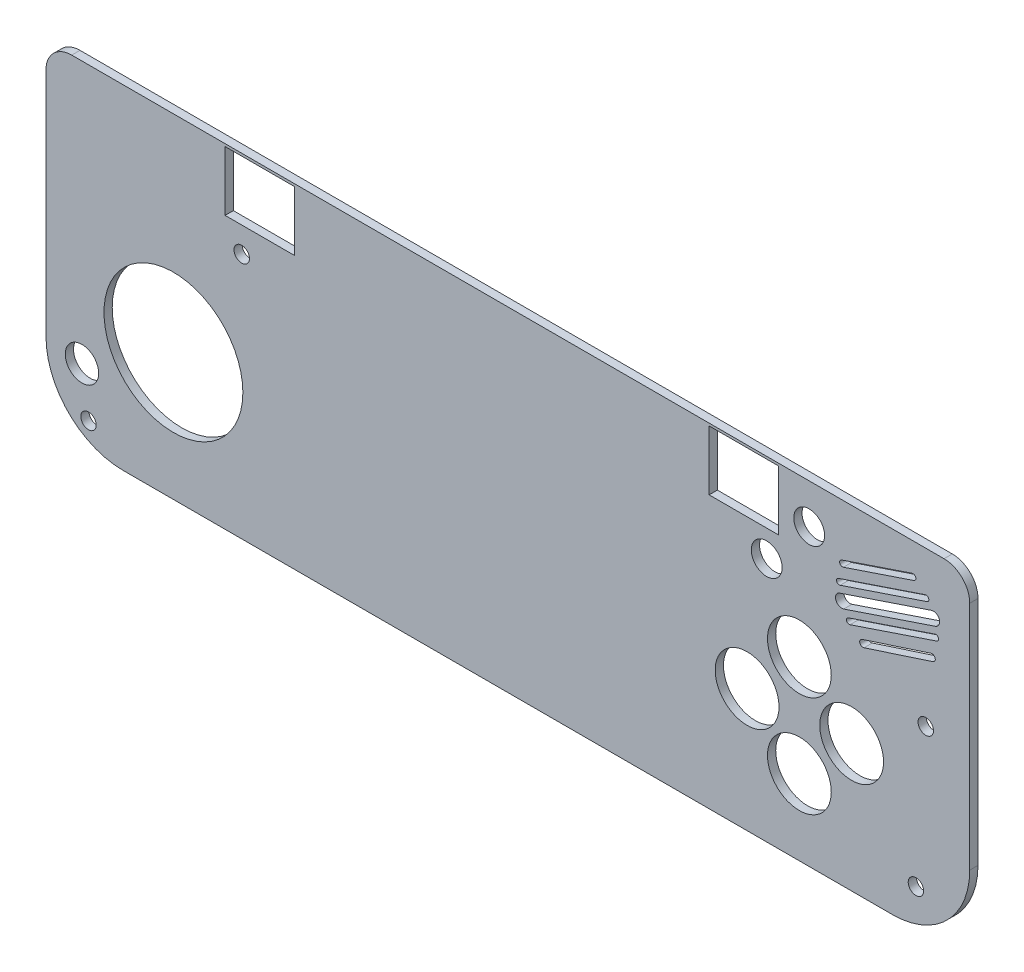
SolidWorks part; units mm, degrees
other "Caméra1"
ref_plane "Plan de face" through (0, 0, 0) normal (0, 0, 1) x (1, 0, 0)
ref_plane "Plan de dessus" through (0, 0, 0) normal (0, 1, 0) x (1, 0, 0)
ref_plane "Plan de droite" through (0, 0, 0) normal (1, 0, 0) x (0, 0, -1)
sketch "Esquisse20" plane through (0, 0, 0) normal (0, 0, 1) x (1, 0, 0)
  line L1 (15, -2.2) -> (164.57, -2.2)
  line L2 (0, 12.8) -> (0, 57.73)
  line L3 (5, 62.73) -> (174.57, 62.73)
  line L4 (179.57, 12.8) -> (179.57, 57.73)
  arc A0 (0, 57.73) -> (5, 62.73) centre (5, 57.73) cw
  arc A1 (174.57, 62.73) -> (179.57, 57.73) centre (174.57, 57.73) cw
  arc A2 (164.57, -2.2) -> (179.57, 12.8) centre (164.57, 12.8) ccw
  arc A3 (15, -2.2) -> (0, 12.8) centre (15, 12.8) cw
  point P0 (1.4645, 61.2655)
  point P7 (0, 62.73)
  point P10 (179.57, 62.73)
  point P14 (179.57, -2.2)
  point P17 (0, -2.2)
extrude "Boss.-Extru.1" add sketch "Esquisse20" along normal blind 1.6051
sketch "Esquisse22" plane through (0, 0, 1.6051) normal (0, 0, 1) x (1, 0, 0)
  line L0 (15, -2.2) -> (164.57, -2.2) construction
  line L1 (0, 57.73) -> (0, 12.8) construction
  circle A0 centre (24.77, 22.57) radius 13.5
  dimension "D1" = 24.77
  dimension "D2" = 24.77
extrude "Enlèv. mat.-Extru.1" cut sketch "Esquisse22" against normal blind 2.5
sketch "Esquisse23" plane through (0, 0, 1.6051) normal (0, 0, 1) x (1, 0, 0)
  line L0 (15, -2.2) -> (164.57, -2.2) construction
  line L1 (0, 57.73) -> (0, 12.8) construction
  circle A0 centre (6.99, 11.77) radius 3.25
  circle A1 centre (-24.9782, 23.5691) radius 3.25
  dimension "D1" = 13.97
  dimension "D2" = 6.99
extrude "Enlèv. mat.-Extru.2" cut sketch "Esquisse23" against normal blind 2.5
sketch "Esquisse24" plane through (0, 0, 1.6051) normal (0, 0, 1) x (1, 0, 0)
  line L0 (34.82, 59.37) -> (48.32, 50.65)
  line L1 (34.82, 59.37) -> (48.32, 59.37)
  line L2 (34.82, 59.37) -> (34.82, 50.65)
  line L3 (34.82, 50.65) -> (48.32, 50.65)
  line L4 (48.32, 59.37) -> (48.32, 50.65)
  line L5 (179.57, 12.8) -> (179.57, 57.73) construction
  line L7 (174.57, 62.73) -> (5, 62.73) construction
  point P4 (41.57, 55.01)
  dimension "D1" = 13.5
  dimension "D2" = 8.72
  dimension "D3" = 138
  dimension "D4" = 7.72
extrude "Enlèv. mat.-Extru.3" cut sketch "Esquisse24" against normal blind 2.5 contours L2 L3 L0 | L4 L1 L0 region at (43.82, 56.4633, 1.6051) region at (39.32, 53.5567, 1.6051)
sketch "Esquisse25" plane through (0, 0, 1.6051) normal (0, 0, 1) x (1, 0, 0)
  line L0 (48.32, 59.37) -> (34.82, 59.37)
  line L1 (48.32, 59.37) -> (48.32, 62.2418)
  line L2 (34.82, 59.37) -> (34.82, 62.2418)
  line L3 (48.32, 62.2418) -> (34.82, 62.2418)
extrude "Enlèv. mat.-Extru.4" cut sketch "Esquisse25" against normal blind 2.5
fillet "Congé1" radius 2 rebuild error yes
sketch "Esquisse26" plane through (0, 0, 1.6051) normal (0, 0, 1) x (1, 0, 0)
  line L0 (179.57, 12.8) -> (179.57, 57.73) construction
  line L1 (174.57, 62.73) -> (5, 62.73) construction
  circle A1 centre (156.61, 22.63) radius 6.2
  dimension "D2" = 22.96
  dimension "D3" = 40.1
sketch "Esquisse27" plane through (0, 0, 1.6051) normal (0, 0, 1) x (1, 0, 0)
  line L0 (179.57, 12.8) -> (179.57, 57.73) construction
  line L1 (174.57, 62.73) -> (5, 62.73) construction
  circle A0 centre (146.45, 12.47) radius 6.2
  circle A1 centre (136.29, 21.73) radius 6.2
  circle A2 centre (146.45, 32.15) radius 6.2
  dimension "D1" = 33.12
  dimension "D2" = 43.28
  dimension "D3" = 33.12
  dimension "D4" = 30.58
  dimension "D5" = 41
  dimension "D6" = 50.26
extrude "Enlèv. mat.-Extru.5" cut sketch "Esquisse26" against normal blind 2.5
extrude "Enlèv. mat.-Extru.6" cut sketch "Esquisse27" against normal blind 2.5
sketch "Esquisse30" plane through (0, 0, 1.6051) normal (0, 0, 1) x (1, 0, 0)
  line L0 (128.91, 59.37) -> (142.41, 50.65)
  line L1 (128.91, 59.37) -> (142.41, 59.37)
  line L2 (128.91, 59.37) -> (128.91, 50.65)
  line L3 (128.91, 50.65) -> (142.41, 50.65)
  line L4 (142.41, 59.37) -> (142.41, 50.65)
  line L5 (142.41, 59.37) -> (128.91, 50.65)
  line L6 (174.57, 62.73) -> (5, 62.73) construction
  line L7 (179.57, 12.8) -> (179.57, 57.73) construction
  line L8 (142.41, 59.37) -> (128.91, 59.37)
  line L9 (142.41, 59.37) -> (142.41, 62.2543)
  line L10 (128.91, 59.37) -> (128.91, 62.2543)
  line L11 (142.41, 62.2543) -> (128.91, 62.2543)
  point P4 (135.66, 55.01)
  line M7 (174.57, 62.73) -> (5, 62.73)
  dimension "D1" = 13.5
  dimension "D2" = 8.72
  dimension "D3" = 7.72
  dimension "D4" = 43.91
extrude "Enlèv. mat.-Extru.7" cut sketch "Esquisse30" against normal blind 2.5 contours L10 L1 L9 M7 | L5 L1 L0 | L5 L0 L2 | L0 L5 L3 | L4 L5 L0 region at (135.66, 57.9167, 1.6051) region at (135.66, 60.8122, 1.6051) region at (131.16, 55.01, 1.6051) region at (140.16, 55.01, 1.6051) region at (135.66, 52.1033, 1.6051)
fillet "Congé2" radius 2 rebuild error yes
sketch "Esquisse31" plane through (0, 0, 1.6051) normal (0, 0, 1) x (1, 0, 0)
  line L0 (174.57, 62.73) -> (5, 62.73) construction
  line L1 (179.57, 12.8) -> (179.57, 57.73) construction
  circle A0 centre (148.36, 55.01) radius 3
  circle A1 centre (140.1, 45.49) radius 3
  dimension "D1" = 7.72
  dimension "D3" = 17.24
  dimension "D2" = 31.21
  dimension "D4" = 39.47
extrude "Enlèv. mat.-Extru.8" cut sketch "Esquisse31" against normal blind 2.5
sketch "Esquisse32" plane through (0, 0, 1.6051) normal (0, 0, 1) x (1, 0, 0)
  line L0 (179.57, 12.8) -> (179.57, 57.73) construction
  line L1 (174.57, 62.73) -> (5, 62.73) construction
  line L2 (172.5084, 51.66) -> (154.6916, 45.66) construction
  line L3 (172.8949, 50.5123) -> (155.0781, 44.5123)
  line L4 (172.1219, 52.8077) -> (154.3051, 46.8077)
  line L5 (154.2, 48.66) -> (171.0851, 54.3462) construction
  line L6 (154.0321, 49.1585) -> (170.9172, 54.8448)
  line L7 (154.3679, 48.1615) -> (171.253, 53.8477)
  line L8 (154.8275, 52.0369) -> (168.5427, 56.6556) construction
  line L9 (154.6512, 52.5603) -> (168.3664, 57.1791)
  line L10 (155.0038, 51.5134) -> (168.719, 56.1321)
  line L11 (156.1149, 42.9738) -> (173, 48.66) construction
  line L12 (155.9468, 43.4729) -> (172.8319, 49.1592)
  line L13 (156.283, 42.4746) -> (173.1681, 48.1608)
  line L14 (158.8161, 40.5684) -> (172.2294, 44.9325) construction
  line L17 (158.6179, 41.1774) -> (172.0312, 45.5415)
  line L18 (159.0142, 39.9594) -> (172.4275, 44.3235)
  circle A0 centre (163.6, 48.66) radius 10
  circle A1 centre (163.6, 48.66) radius 9.4
  arc A2 (172.8949, 50.5123) -> (172.1219, 52.8077) centre (172.5084, 51.66) ccw
  arc A3 (154.3051, 46.8077) -> (155.0781, 44.5123) centre (154.6916, 45.66) ccw
  arc A4 (154.0321, 49.1585) -> (154.3679, 48.1615) centre (154.2, 48.66) ccw
  arc A5 (171.253, 53.8477) -> (170.9172, 54.8448) centre (171.0851, 54.3462) ccw
  arc A6 (154.6512, 52.5603) -> (155.0038, 51.5134) centre (154.8275, 52.0369) ccw
  arc A7 (168.719, 56.1321) -> (168.3664, 57.1791) centre (168.5427, 56.6556) ccw
  arc A8 (155.9468, 43.4729) -> (156.283, 42.4746) centre (156.1149, 42.9738) ccw
  arc A9 (173.1681, 48.1608) -> (172.8319, 49.1592) centre (173, 48.66) ccw
  arc A12 (158.6179, 41.1774) -> (159.0142, 39.9594) centre (158.8161, 40.5684) ccw
  arc A13 (172.4275, 44.3235) -> (172.0312, 45.5415) centre (172.2294, 44.9325) ccw
  point P9 (163.6, 48.66)
  point P16 (162.6426, 51.5031)
  point P23 (161.6851, 54.3462)
  point P30 (164.5574, 45.8169)
  point P37 (165.5227, 42.7505)
  dimension "D1" = 15.97
  dimension "D3" = 0.589
  dimension "D2" = 14.07
  dimension "D4" = 3
  dimension "D5" = 3
  dimension "D6" = 3
extrude "Enlèv. mat.-Extru.9" cut sketch "Esquisse32" against normal blind 2.5 contours L10 A7 L9 A6 | L7 A5 L6 A4 | L3 A3 L4 A2 | L13 A9 L12 A8 | L18 A13 L17 A12
sketch "Esquisse33" plane through (0, 0, 1.6051) normal (0, 0, 1) x (1, 0, 0)
  circle A0 centre (38.0467, 45.7343) radius 1.5
extrude "Enlèv. mat.-Extru.10" cut sketch "Esquisse33" against normal blind 10
sketch "Esquisse34" plane through (0, 0, 1.6051) normal (0, 0, 1) x (1, 0, 0)
  line L0 (15, -2.2) -> (164.57, -2.2) construction
  line L1 (0, 57.73) -> (0, 12.8) construction
  circle A0 centre (8.26, 2.79) radius 1.5
  dimension "D1" = 4.99
  dimension "D2" = 8.26
extrude "Enlèv. mat.-Extru.11" cut sketch "Esquisse34" against normal blind 10
sketch "Esquisse35" plane through (0, 0, 1.6051) normal (0, 0, 1) x (1, 0, 0)
  line L0 (15, -2.2) -> (164.57, -2.2) construction
  line L1 (179.57, 12.8) -> (179.57, 57.73) construction
  circle A0 centre (169.11, 4.8) radius 1.5
  dimension "D1" = 3
  dimension "D2" = 7
  dimension "D3" = 10.46
extrude "Enlèv. mat.-Extru.12" cut sketch "Esquisse35" against normal blind 10
sketch "Esquisse36" plane through (0, 0, 1.6051) normal (0, 0, 1) x (1, 0, 0)
  line L0 (179.57, 12.8) -> (179.57, 57.73) construction
  line L1 (174.57, 62.73) -> (5, 62.73) construction
  circle A0 centre (171.02, 32.73) radius 1.5
  dimension "D1" = 8.55
  dimension "D2" = 30
extrude "Enlèv. mat.-Extru.13" cut sketch "Esquisse36" against normal blind 10
